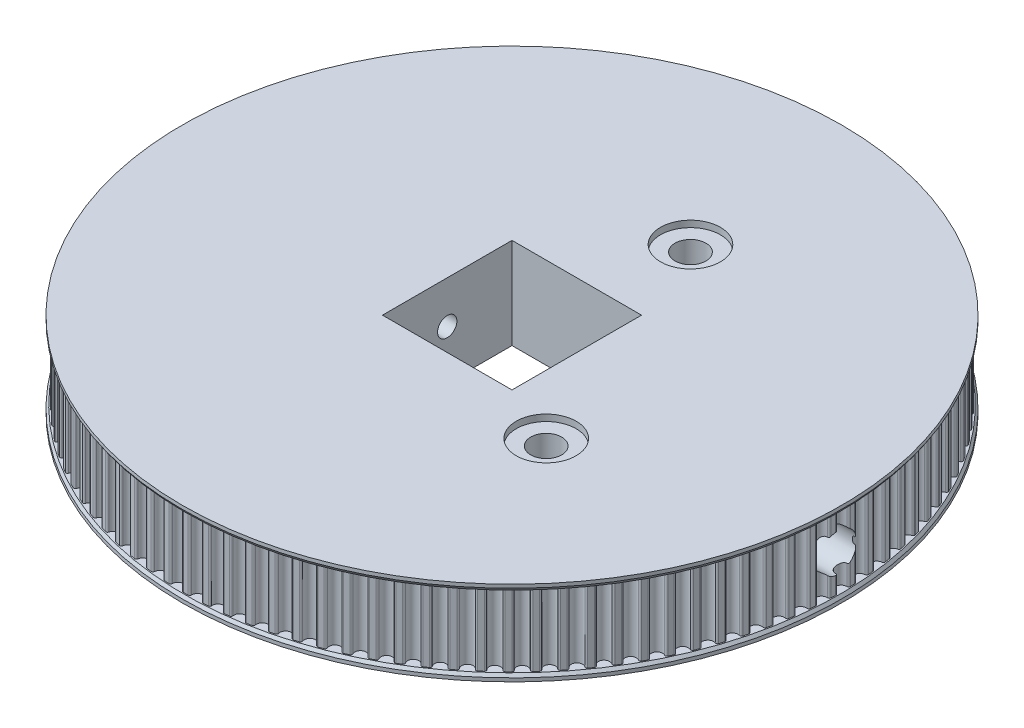
SolidWorks part; units mm, degrees
ref_plane "Front Plane" through (0, 0, 0) normal (0, 0, 1) x (1, 0, 0)
ref_plane "Top Plane" through (0, 0, 0) normal (0, 1, 0) x (1, 0, 0)
ref_plane "Right Plane" through (0, 0, 0) normal (1, 0, 0) x (0, 0, -1)
sketch "Sketch1" plane through (0, 0, 0) normal (0, 1, 0) x (1, 0, 0)
  arc A2 (0, 48.9563) -> (0.8696, 49.853) centre (0, 49.8263) ccw
  arc A3 (2.1134, 49.8158) -> (2.9278, 48.8687) centre (2.9798, 49.7371) ccw
  arc A4 (1.1354, 50.121) -> (0.8696, 49.853) centre (1.1295, 49.861) ccw
  arc A5 (2.1134, 49.8158) -> (1.8641, 50.0991) centre (1.8545, 49.8393) ccw
  arc A6 (1.8641, 50.0991) -> (1.1354, 50.121) centre (0, 0) ccw
  arc A7 (2.9278, 48.8687) -> (3.8495, 49.7118) centre (2.9798, 49.7371) ccw
  arc A8 (4.1308, 49.9633) -> (3.8495, 49.7118) centre (4.1093, 49.7042) ccw
  arc A9 (4.8569, 49.898) -> (4.1308, 49.9633) centre (0, 0) ccw
  arc A10 (5.0888, 49.6003) -> (4.8569, 49.898) centre (4.8317, 49.6392) ccw
  arc A11 (5.0888, 49.6003) -> (5.8451, 48.6061) centre (5.949, 49.4699) ccw
  arc A12 (5.8451, 48.6061) -> (6.8155, 49.3926) centre (5.949, 49.4699) ccw
  arc A13 (7.1114, 49.6269) -> (6.8155, 49.3926) centre (7.0745, 49.3695) ccw
  arc A14 (7.8323, 49.5182) -> (7.1114, 49.6269) centre (0, 0) ccw
  arc A15 (8.046, 49.2071) -> (7.8323, 49.5182) centre (7.7917, 49.2614) ccw
  arc A16 (8.046, 49.2071) -> (8.7415, 48.1696) centre (8.8968, 49.0256) ccw
  arc A17 (8.7415, 48.1696) -> (9.7572, 48.8966) centre (8.8968, 49.0256) ccw
  arc A18 (10.0666, 49.1128) -> (9.7572, 48.8966) centre (10.0143, 48.8581) ccw
  arc A19 (10.7797, 48.9612) -> (10.0666, 49.1128) centre (0, 0) ccw
  arc A20 (10.9744, 48.6379) -> (10.7797, 48.9612) centre (10.7238, 48.7073) ccw
  arc A21 (10.9744, 48.6379) -> (11.6066, 47.5606) centre (11.8128, 48.4058) ccw
  arc A22 (11.6066, 47.5606) -> (12.664, 48.2256) centre (11.8128, 48.4058) ccw
  arc A23 (12.9857, 48.4228) -> (12.664, 48.2256) centre (12.9183, 48.1717) ccw
  arc A24 (13.6885, 48.2289) -> (12.9857, 48.4228) centre (0, 0) ccw
  arc A25 (13.8635, 47.8945) -> (13.6885, 48.2289) centre (13.6175, 47.9787) ccw
  arc A26 (13.8635, 47.8945) -> (14.4301, 46.7813) centre (14.6866, 47.6127) ccw
  arc A27 (14.4301, 46.7813) -> (15.5254, 47.3819) centre (14.6866, 47.6127) ccw
  arc A28 (15.8583, 47.5596) -> (15.5254, 47.3819) centre (15.7761, 47.3129) ccw
  arc A29 (16.5483, 47.3239) -> (15.8583, 47.5596) centre (0, 0) ccw
  arc A30 (16.703, 46.9797) -> (16.5483, 47.3239) centre (16.4625, 47.0785) ccw
  arc A31 (16.703, 46.9797) -> (17.202, 45.8346) centre (17.5077, 46.6491) ccw
  arc A32 (17.202, 45.8346) -> (18.3312, 46.3686) centre (17.5077, 46.6491) ccw
  arc A33 (18.6742, 46.526) -> (18.3312, 46.3686) centre (18.5774, 46.2848) ccw
  arc A34 (19.3488, 46.2496) -> (18.6742, 46.526) centre (0, 0) ccw
  arc A35 (19.4826, 45.8967) -> (19.3488, 46.2496) centre (19.2485, 46.0097) ccw
  arc A36 (19.4826, 45.8967) -> (19.9123, 44.7238) centre (20.2662, 45.5186) ccw
  arc A37 (19.9123, 44.7238) -> (21.0715, 45.1893) centre (20.2662, 45.5186) ccw
  arc A38 (21.4232, 45.326) -> (21.0715, 45.1893) centre (21.3121, 45.0909) ccw
  arc A39 (22.0801, 45.0096) -> (21.4232, 45.326) centre (0, 0) ccw
  arc A40 (22.1926, 44.6494) -> (22.0801, 45.0096) centre (21.9656, 44.7762) ccw
  arc A41 (22.1926, 44.6494) -> (22.5514, 43.4529) centre (22.9521, 44.2251) ccw
  arc A42 (22.5514, 43.4529) -> (23.7363, 43.8483) centre (22.9521, 44.2251) ccw
  arc A43 (24.0956, 43.9637) -> (23.7363, 43.8483) centre (23.9706, 43.7356) ccw
  arc A44 (24.7324, 43.6086) -> (24.0956, 43.9637) centre (0, 0) ccw
  arc A45 (24.8231, 43.2423) -> (24.7324, 43.6086) centre (24.6041, 43.3824) ccw
  arc A46 (24.8231, 43.2423) -> (25.1097, 42.0265) centre (25.5559, 42.7733) ccw
  arc A47 (25.1097, 42.0265) -> (26.3161, 42.3503) centre (25.5559, 42.7733) ccw
  arc A48 (26.6816, 42.4439) -> (26.3161, 42.3503) centre (26.5433, 42.2238) ccw
  arc A49 (27.2961, 42.0514) -> (26.6816, 42.4439) centre (0, 0) ccw
  arc A50 (27.3647, 41.6804) -> (27.2961, 42.0514) centre (27.1545, 41.8334) ccw
  arc A51 (27.3647, 41.6804) -> (27.5781, 40.4496) centre (28.0682, 41.1684) ccw
  arc A52 (27.5781, 40.4496) -> (28.8017, 40.7006) centre (28.0682, 41.1684) ccw
  arc A53 (29.1722, 40.7723) -> (28.8017, 40.7006) centre (29.0209, 40.5609) ccw
  arc A54 (29.7621, 40.3438) -> (29.1722, 40.7723) centre (0, 0) ccw
  arc A55 (29.8084, 39.9692) -> (29.7621, 40.3438) centre (29.6077, 40.1345) ccw
  arc A56 (29.8084, 39.9692) -> (29.9478, 38.7279) centre (30.48, 39.4161) ccw
  arc A57 (29.9478, 38.7279) -> (31.1842, 38.9053) centre (30.48, 39.4161) ccw
  arc A58 (31.5583, 38.9547) -> (31.1842, 38.9053) centre (31.3947, 38.7527) ccw
  arc A59 (32.1215, 38.4917) -> (31.5583, 38.9547) centre (0, 0) ccw
  arc A60 (32.1454, 38.115) -> (32.1215, 38.4917) centre (31.9549, 38.292) ccw
  arc A61 (32.1454, 38.115) -> (32.2103, 36.8676) centre (32.7827, 37.5228) ccw
  arc A62 (32.2103, 36.8676) -> (33.4551, 36.9708) centre (32.7827, 37.5228) ccw
  arc A63 (33.8315, 36.9977) -> (33.4551, 36.9708) centre (33.6561, 36.8058) ccw
  arc A64 (34.366, 36.5018) -> (33.8315, 36.9977) centre (0, 0) ccw
  arc A65 (34.3673, 36.1244) -> (34.366, 36.5018) centre (34.1878, 36.3125) ccw
  arc A66 (34.3673, 36.1244) -> (34.3574, 34.8753) centre (34.968, 35.4951) ccw
  arc A67 (34.3574, 34.8753) -> (35.6062, 34.9038) centre (34.968, 35.4951) ccw
  arc A68 (35.9836, 34.9082) -> (35.6062, 34.9038) centre (35.797, 34.7271) ccw
  arc A69 (36.4874, 34.3812) -> (35.9836, 34.9082) centre (0, 0) ccw
  arc A70 (36.4662, 34.0044) -> (36.4874, 34.3812) centre (36.2982, 34.2029) ccw
  arc A71 (36.4662, 34.0044) -> (36.3816, 32.7582) centre (37.0282, 33.3403) ccw
  arc A72 (36.3816, 32.7582) -> (37.6299, 32.712) centre (37.0282, 33.3403) ccw
  arc A73 (38.0068, 32.6937) -> (37.6299, 32.712) centre (37.8097, 32.5242) ccw
  arc A74 (38.4783, 32.1376) -> (38.0068, 32.6937) centre (0, 0) ccw
  arc A75 (38.4345, 31.7627) -> (38.4783, 32.1376) centre (38.2787, 31.9709) ccw
  arc A76 (38.4345, 31.7627) -> (38.2756, 30.5238) centre (38.9558, 31.0662) ccw
  arc A77 (38.2756, 30.5238) -> (39.5188, 30.403) centre (38.9558, 31.0662) ccw
  arc A78 (39.894, 30.3622) -> (39.5188, 30.403) centre (39.6871, 30.2048) ccw
  arc A79 (40.3313, 29.7789) -> (39.894, 30.3622) centre (0, 0) ccw
  arc A80 (40.2652, 29.4073) -> (40.3313, 29.7789) centre (40.1222, 29.6244) ccw
  arc A81 (40.2652, 29.4073) -> (40.0325, 28.1801) centre (40.7439, 28.6809) ccw
  arc A82 (40.0325, 28.1801) -> (41.2663, 27.9852) centre (40.7439, 28.6809) ccw
  arc A83 (41.6384, 27.9221) -> (41.2663, 27.9852) centre (41.4225, 27.7773) ccw
  arc A84 (42.0401, 27.3136) -> (41.6384, 27.9221) centre (0, 0) ccw
  arc A85 (41.9519, 26.9467) -> (42.0401, 27.3136) centre (41.822, 27.1719) ccw
  arc A86 (41.9519, 26.9467) -> (41.6462, 25.7355) centre (42.3862, 26.1929) ccw
  arc A87 (41.6462, 25.7355) -> (42.8661, 25.4672) centre (42.3862, 26.1929) ccw
  arc A88 (43.2337, 25.3819) -> (42.8661, 25.4672) centre (43.0095, 25.2503) ccw
  arc A89 (43.5983, 24.7505) -> (43.2337, 25.3819) centre (0, 0) ccw
  arc A90 (43.4883, 24.3895) -> (43.5983, 24.7505) centre (43.3722, 24.6222) ccw
  arc A91 (43.4883, 24.3895) -> (43.1107, 23.1989) centre (43.8768, 23.6111) ccw
  arc A92 (43.1107, 23.1989) -> (44.3124, 22.858) centre (43.8768, 23.6111) ccw
  arc A93 (44.6743, 22.751) -> (44.3124, 22.858) centre (44.4426, 22.633) ccw
  arc A94 (45.0004, 22.0989) -> (44.6743, 22.751) centre (0, 0) ccw
  arc A95 (44.869, 21.7451) -> (45.0004, 22.0989) centre (44.767, 21.9843) ccw
  arc A96 (44.869, 21.7451) -> (44.4209, 20.5791) centre (45.2103, 20.9448) ccw
  arc A97 (44.4209, 20.5791) -> (45.6001, 20.1671) centre (45.2103, 20.9448) ccw
  arc A98 (45.9549, 20.0385) -> (45.6001, 20.1671) centre (45.7166, 19.9346) ccw
  arc A99 (46.2415, 19.3681) -> (45.9549, 20.0385) centre (0, 0) ccw
  arc A100 (46.0892, 19.0228) -> (46.2415, 19.3681) centre (46.0017, 19.2677) ccw
  arc A101 (46.0892, 19.0228) -> (45.5721, 17.8857) centre (46.382, 18.2036) ccw
  arc A102 (45.5721, 17.8857) -> (46.7246, 17.4039) centre (46.382, 18.2036) ccw
  arc A103 (47.0711, 17.2544) -> (46.7246, 17.4039) centre (46.827, 17.1649) ccw
  arc A104 (47.317, 16.568) -> (47.0711, 17.2544) centre (0, 0) ccw
  arc A105 (47.1443, 16.2325) -> (47.317, 16.568) centre (47.0716, 16.4821) ccw
  arc A106 (47.1443, 16.2325) -> (46.5602, 15.1283) centre (47.3876, 15.3972) ccw
  arc A107 (46.5602, 15.1283) -> (47.6818, 14.5784) centre (47.3876, 15.3972) ccw
  arc A108 (48.0187, 14.4084) -> (47.6818, 14.5784) centre (47.7697, 14.3337) ccw
  arc A109 (48.2232, 13.7086) -> (48.0187, 14.4084) centre (0, 0) ccw
  arc A110 (48.0307, 13.384) -> (48.2232, 13.7086) centre (47.9731, 13.6375) ccw
  arc A111 (48.0307, 13.384) -> (47.3816, 12.3168) centre (48.2236, 12.5356) ccw
  arc A112 (47.3816, 12.3168) -> (48.4683, 11.7007) centre (48.2236, 12.5356) ccw
  arc A113 (48.7944, 11.5109) -> (48.4683, 11.7007) centre (48.5414, 11.4512) ccw
  arc A114 (48.9567, 10.8001) -> (48.7944, 11.5109) centre (0, 0) ccw
  arc A115 (48.7452, 10.4876) -> (48.9567, 10.8001) centre (48.7028, 10.7441) ccw
  arc A116 (48.7452, 10.4876) -> (48.0334, 9.4611) centre (48.887, 9.6292) ccw
  arc A117 (48.0334, 9.4611) -> (49.0813, 8.7812) centre (48.887, 9.6292) ccw
  arc A118 (49.3955, 8.5722) -> (49.0813, 8.7812) centre (49.1393, 8.5278) ccw
  arc A119 (49.5149, 7.853) -> (49.3955, 8.5722) centre (0, 0) ccw
  arc A120 (49.2851, 7.5537) -> (49.5149, 7.853) centre (49.2582, 7.8123) ccw
  arc A121 (49.2851, 7.5537) -> (48.5132, 6.5716) centre (49.3754, 6.6883) ccw
  arc A122 (48.5132, 6.5716) -> (49.5186, 5.8302) centre (49.3754, 6.6883) ccw
  arc A123 (49.8197, 5.6028) -> (49.5186, 5.8302) centre (49.5614, 5.5738) ccw
  arc A124 (49.896, 4.8777) -> (49.8197, 5.6028) centre (0, 0) ccw
  arc A125 (49.6486, 4.5927) -> (49.896, 4.8777) centre (49.6372, 4.8524) ccw
  arc A126 (49.6486, 4.5927) -> (48.8194, 3.6585) centre (49.687, 3.7235) ccw
  arc A127 (48.8194, 3.6585) -> (49.7786, 2.8584) centre (49.687, 3.7235) ccw
  arc A128 (50.0656, 2.6134) -> (49.7786, 2.8584) centre (49.806, 2.5998) ccw
  arc A129 (50.0984, 1.885) -> (50.0656, 2.6134) centre (0, 0) ccw
  arc A130 (49.8344, 1.6153) -> (50.0984, 1.885) centre (49.8385, 1.8752) ccw
  arc A131 (49.8344, 1.6153) -> (48.9508, 0.7324) centre (49.8207, 0.7454) ccw
  arc A132 (48.9508, 0.7324) -> (49.8605, -0.1237) centre (49.8207, 0.7454) ccw
  arc A133 (50.1323, -0.3854) -> (49.8605, -0.1237) centre (49.8723, -0.3834) ccw
  arc A134 (50.1214, -1.1145) -> (50.1323, -0.3854) centre (0, 0) ccw
  arc A135 (49.8418, -1.3679) -> (50.1214, -1.1145) centre (49.8615, -1.1087) ccw
  arc A136 (49.8418, -1.3679) -> (48.907, -2.1964) centre (49.7761, -2.2354) ccw
  arc A137 (48.907, -2.1964) -> (49.7638, -3.1054) centre (49.7761, -2.2354) ccw
  arc A138 (50.0195, -3.3829) -> (49.7638, -3.1054) centre (49.7601, -3.3653) ccw
  arc A139 (49.9651, -4.1099) -> (50.0195, -3.3829) centre (0, 0) ccw
  arc A140 (49.6708, -4.3462) -> (49.9651, -4.1099) centre (49.7059, -4.0886) ccw
  arc A141 (49.6708, -4.3462) -> (48.6881, -5.1173) centre (49.5534, -5.2083) ccw
  arc A142 (48.6881, -5.1173) -> (49.489, -6.0759) centre (49.5534, -5.2083) ccw
  arc A143 (49.7277, -6.3682) -> (49.489, -6.0759) centre (49.4698, -6.3352) ccw
  arc A144 (49.6298, -7.0907) -> (49.7277, -6.3682) centre (0, 0) ccw
  arc A145 (49.322, -7.309) -> (49.6298, -7.0907) centre (49.3725, -7.0539) ccw
  arc A146 (49.322, -7.309) -> (48.2949, -8.0199) centre (49.1532, -8.1624) ccw
  arc A147 (48.2949, -8.0199) -> (49.0371, -9.0247) centre (49.1532, -8.1624) ccw
  arc A148 (49.2579, -9.3307) -> (49.0371, -9.0247) centre (49.0024, -9.2823) ccw
  arc A149 (49.117, -10.0461) -> (49.2579, -9.3307) centre (0, 0) ccw
  arc A150 (48.7966, -10.2456) -> (49.117, -10.0461) centre (48.8622, -9.994) ccw
  arc A151 (48.7966, -10.2456) -> (47.7289, -10.8938) centre (48.5771, -11.0874) ccw
  arc A152 (47.7289, -10.8938) -> (48.4096, -11.9411) centre (48.5771, -11.0874) ccw
  arc A153 (48.6117, -12.2598) -> (48.4096, -11.9411) centre (48.3596, -12.1963) ccw
  arc A154 (48.4282, -12.9655) -> (48.6117, -12.2598) centre (0, 0) ccw
  arc A155 (48.0965, -13.1455) -> (48.4282, -12.9655) centre (48.1771, -12.8982) ccw
  arc A156 (48.0965, -13.1455) -> (46.9919, -13.7287) centre (47.827, -13.9727) ccw
  arc A157 (46.9919, -13.7287) -> (47.6088, -14.8149) centre (47.827, -13.9727) ccw
  arc A158 (47.7915, -15.1451) -> (47.6088, -14.8149) centre (47.5436, -15.0665) ccw
  arc A159 (47.5662, -15.8385) -> (47.7915, -15.1451) centre (0, 0) ccw
  arc A160 (47.2243, -15.9983) -> (47.5662, -15.8385) centre (47.3195, -15.7564) ccw
  arc A161 (47.2243, -15.9983) -> (46.0868, -16.5144) centre (46.9058, -16.8079) ccw
  arc A162 (46.0868, -16.5144) -> (46.6376, -17.6355) centre (46.9058, -16.8079) ccw
  arc A163 (46.8002, -17.9761) -> (46.6376, -17.6355) centre (46.5575, -17.8829) ccw
  arc A164 (46.5338, -18.6548) -> (46.8002, -17.9761) centre (0, 0) ccw
  arc A165 (46.183, -18.7939) -> (46.5338, -18.6548) centre (46.2925, -18.5581) ccw
  arc A166 (46.183, -18.7939) -> (45.0167, -19.2411) centre (45.8167, -19.583) ccw
  arc A167 (45.0167, -19.2411) -> (45.4995, -20.3931) centre (45.8167, -19.583) ccw
  arc A168 (45.6414, -20.7428) -> (45.4995, -20.3931) centre (45.4047, -20.6352) ccw
  arc A169 (45.3349, -21.4043) -> (45.6414, -20.7428) centre (0, 0) ccw
  arc A170 (44.9764, -21.5222) -> (45.3349, -21.4043) centre (45.0998, -21.2933) ccw
  arc A171 (44.9764, -21.5222) -> (43.7854, -21.8988) centre (44.5635, -22.288) ccw
  arc A172 (43.7854, -21.8988) -> (44.1984, -23.0777) centre (44.5635, -22.288) ccw
  arc A173 (44.3192, -23.4352) -> (44.1984, -23.0777) centre (44.0893, -23.3137) ccw
  arc A174 (43.9737, -24.0772) -> (44.3192, -23.4352) centre (0, 0) ccw
  arc A175 (43.6088, -24.1734) -> (43.9737, -24.0772) centre (43.7456, -23.9524) ccw
  arc A176 (43.6088, -24.1734) -> (42.3974, -24.4782) centre (43.1508, -24.9132) ccw
  arc A177 (42.3974, -24.4782) -> (42.7392, -25.6796) centre (43.1508, -24.9132) ccw
  arc A178 (42.8383, -26.0437) -> (42.7392, -25.6796) centre (42.6162, -25.9087) ccw
  arc A179 (42.4551, -26.6639) -> (42.8383, -26.0437) centre (0, 0) ccw
  arc A180 (42.0851, -26.7381) -> (42.4551, -26.6639) centre (42.2349, -26.5257) ccw
  arc A181 (42.0851, -26.7381) -> (40.8576, -26.9699) centre (41.5837, -27.4492) ccw
  arc A182 (40.8576, -26.9699) -> (41.127, -28.1896) centre (41.5837, -27.4492) ccw
  arc A183 (41.2041, -28.559) -> (41.127, -28.1896) centre (40.9905, -28.4109) ccw
  arc A184 (40.7845, -29.1552) -> (41.2041, -28.559) centre (0, 0) ccw
  arc A185 (40.4107, -29.2072) -> (40.7845, -29.1552) centre (40.573, -29.004) ccw
  arc A186 (40.4107, -29.2072) -> (39.1716, -29.3651) centre (39.8677, -29.8869) ccw
  arc A187 (39.1716, -29.3651) -> (39.3675, -30.5987) centre (39.8677, -29.8869) ccw
  arc A188 (39.4224, -30.9721) -> (39.3675, -30.5987) centre (39.218, -30.8115) ccw
  arc A189 (38.9679, -31.5421) -> (39.4224, -30.9721) centre (0, 0) ccw
  arc A190 (38.5916, -31.5716) -> (38.9679, -31.5421) centre (38.7658, -31.3785) ccw
  arc A191 (38.5916, -31.5716) -> (37.3453, -31.6551) centre (38.009, -32.2177) ccw
  arc A192 (37.3453, -31.6551) -> (37.4671, -32.8983) centre (38.009, -32.2177) ccw
  arc A193 (37.4996, -33.2743) -> (37.4671, -32.8983) centre (37.3051, -33.1017) ccw
  arc A194 (37.0118, -33.8161) -> (37.4996, -33.2743) centre (0, 0) ccw
  arc A195 (36.6345, -33.823) -> (37.0118, -33.8161) centre (36.8198, -33.6407) ccw
  arc A196 (36.6345, -33.823) -> (35.3854, -33.8319) centre (36.0142, -34.4331) ccw
  arc A197 (35.3854, -33.8319) -> (35.4326, -35.0801) centre (36.0142, -34.4331) ccw
  arc A198 (35.4426, -35.4573) -> (35.4326, -35.0801) centre (35.2588, -35.2735) ccw
  arc A199 (34.9232, -35.969) -> (35.4426, -35.4573) centre (0, 0) ccw
  arc A200 (34.5461, -35.9534) -> (34.9232, -35.969) centre (34.7421, -35.7825) ccw
  arc A201 (34.5461, -35.9534) -> (33.2987, -35.8875) centre (33.8905, -36.5253) ccw
  arc A202 (33.2987, -35.8875) -> (33.2712, -37.1363) centre (33.8905, -36.5253) ccw
  arc A203 (33.2586, -37.5135) -> (33.2712, -37.1363) centre (33.0861, -37.3189) ccw
  arc A204 (32.7096, -37.9932) -> (33.2586, -37.5135) centre (0, 0) ccw
  arc A205 (32.3341, -37.955) -> (32.7096, -37.9932) centre (32.5399, -37.7962) ccw
  arc A206 (32.3341, -37.955) -> (31.0929, -37.8147) centre (31.6455, -38.4867) ccw
  arc A207 (31.0929, -37.8147) -> (30.9908, -39.0596) centre (31.6455, -38.4867) ccw
  arc A208 (30.9556, -39.4354) -> (30.9908, -39.0596) centre (30.7951, -39.2308) ccw
  arc A209 (30.3789, -39.8814) -> (30.9556, -39.4354) centre (0, 0) ccw
  arc A210 (30.0064, -39.8208) -> (30.3789, -39.8814) centre (30.2213, -39.6745) ccw
  arc A211 (30.0064, -39.8208) -> (28.7758, -39.6065) centre (29.2872, -40.3103) ccw
  arc A212 (28.7758, -39.6065) -> (28.5994, -40.8431) centre (29.2872, -40.3103) ccw
  arc A213 (28.5418, -41.216) -> (28.5994, -40.8431) centre (28.3938, -41.0023) ccw
  arc A214 (27.9394, -41.6268) -> (28.5418, -41.216) centre (0, 0) ccw
  arc A215 (27.5712, -41.544) -> (27.9394, -41.6268) centre (27.7945, -41.4109) ccw
  arc A216 (27.5712, -41.544) -> (26.3557, -41.2565) centre (26.824, -41.9897) ccw
  arc A217 (26.3557, -41.2565) -> (26.1056, -42.4803) centre (26.824, -41.9897) ccw
  arc A218 (26.0259, -42.8492) -> (26.1056, -42.4803) centre (25.8909, -42.627) ccw
  arc A219 (25.4, -43.2231) -> (26.0259, -42.8492) centre (0, 0) ccw
  arc A220 (25.0374, -43.1186) -> (25.4, -43.2231) centre (25.2682, -42.999) ccw
  arc A221 (25.0374, -43.1186) -> (23.8412, -42.7588) centre (24.2649, -43.5187) ccw
  arc A222 (23.8412, -42.7588) -> (23.5184, -43.9655) centre (24.2649, -43.5187) ccw
  arc A223 (23.4167, -44.329) -> (23.5184, -43.9655) centre (23.2953, -44.0991) ccw
  arc A224 (22.7696, -44.6648) -> (23.4167, -44.329) centre (0, 0) ccw
  arc A225 (22.4139, -44.5387) -> (22.7696, -44.6648) centre (22.6515, -44.4332) ccw
  arc A226 (22.4139, -44.5387) -> (21.2413, -44.1081) centre (21.6188, -44.892) ccw
  arc A227 (21.2413, -44.1081) -> (20.8469, -45.2933) centre (21.6188, -44.892) ccw
  arc A228 (20.7237, -45.65) -> (20.8469, -45.2933) centre (20.6163, -45.4133) ccw
  arc A229 (20.0577, -45.9466) -> (20.7237, -45.65) centre (0, 0) ccw
  arc A230 (19.7102, -45.7995) -> (20.0577, -45.9466) centre (19.9537, -45.7083) ccw
  arc A231 (19.7102, -45.7995) -> (18.5655, -45.2995) centre (18.8954, -46.1045) ccw
  arc A232 (18.5655, -45.2995) -> (18.1009, -46.459) centre (18.8954, -46.1045) ccw
  arc A233 (17.9566, -46.8077) -> (18.1009, -46.459) centre (17.8635, -46.5649) ccw
  arc A234 (17.274, -47.0639) -> (17.9566, -46.8077) centre (0, 0) ccw
  arc A235 (16.9359, -46.8962) -> (17.274, -47.0639) centre (17.1844, -46.8198) ccw
  arc A236 (16.9359, -46.8962) -> (15.8232, -46.3287) centre (16.1043, -47.152) ccw
  arc A237 (15.8232, -46.3287) -> (15.2901, -47.4583) centre (16.1043, -47.152) ccw
  arc A238 (15.1252, -47.7978) -> (15.2901, -47.4583) centre (15.0467, -47.5499) ccw
  arc A239 (14.4285, -48.0127) -> (15.1252, -47.7978) centre (0, 0) ccw
  arc A240 (14.101, -47.8251) -> (14.4285, -48.0127) centre (14.3536, -47.7637) ccw
  arc A241 (14.101, -47.8251) -> (13.0242, -47.1921) centre (13.2556, -48.0307) ccw
  arc A242 (13.0242, -47.1921) -> (12.4245, -48.2878) centre (13.2556, -48.0307) ccw
  arc A243 (12.2396, -48.6168) -> (12.4245, -48.2878) centre (12.1761, -48.3646) ccw
  arc A244 (11.5313, -48.7896) -> (12.2396, -48.6168) centre (0, 0) ccw
  arc A245 (11.2156, -48.5828) -> (11.5313, -48.7896) centre (11.4715, -48.5366) ccw
  arc A246 (11.2156, -48.5828) -> (10.1786, -47.8865) centre (10.3595, -48.7375) ccw
  arc A247 (10.1786, -47.8865) -> (9.5144, -48.9444) centre (10.3595, -48.7375) ccw
  arc A248 (9.3102, -49.2617) -> (9.5144, -48.9444) centre (9.2619, -49.0063) ccw
  arc A249 (8.5928, -49.3919) -> (9.3102, -49.2617) centre (0, 0) ccw
  arc A250 (8.2901, -49.1666) -> (8.5928, -49.3919) centre (8.5483, -49.1358) ccw
  arc A251 (8.2901, -49.1666) -> (7.2966, -48.4095) centre (7.4262, -49.2698) ccw
  arc A252 (7.2966, -48.4095) -> (6.5703, -49.4258) centre (7.4262, -49.2698) ccw
  arc A253 (6.3475, -49.7304) -> (6.5703, -49.4258) centre (6.3145, -49.4724) ccw
  arc A254 (5.6236, -49.8174) -> (6.3475, -49.7304) centre (0, 0) ccw
  arc A255 (5.3349, -49.5744) -> (5.6236, -49.8174) centre (5.5944, -49.559) ccw
  arc A256 (5.3349, -49.5744) -> (4.3884, -48.7592) centre (4.4664, -49.6257) ccw
  arc A257 (4.3884, -48.7592) -> (3.6027, -49.7303) centre (4.4664, -49.6257) ccw
  arc A258 (3.362, -50.021) -> (3.6027, -49.7303) centre (3.3446, -49.7615) ccw
  arc A259 (2.6342, -50.0646) -> (3.362, -50.021) centre (0, 0) ccw
  arc A260 (2.3606, -49.8047) -> (2.6342, -50.0646) centre (2.6206, -49.8049) ccw
  arc A261 (2.3606, -49.8047) -> (1.4646, -48.9344) centre (1.4906, -49.804) ccw
  arc A262 (1.4646, -48.9344) -> (0.6222, -49.8567) centre (1.4906, -49.804) ccw
  arc A263 (0.3645, -50.1325) -> (0.6222, -49.8567) centre (0.3627, -49.8725) ccw
  arc A264 (-0.3645, -50.1325) -> (0.3645, -50.1325) centre (0, 0) ccw
  arc A265 (-0.6222, -49.8567) -> (-0.3645, -50.1325) centre (-0.3627, -49.8725) ccw
  arc A266 (-0.6222, -49.8567) -> (-1.4646, -48.9344) centre (-1.4906, -49.804) ccw
  arc A267 (-1.4646, -48.9344) -> (-2.3606, -49.8047) centre (-1.4906, -49.804) ccw
  arc A268 (-2.6342, -50.0646) -> (-2.3606, -49.8047) centre (-2.6206, -49.8049) ccw
  arc A269 (-3.362, -50.021) -> (-2.6342, -50.0646) centre (0, 0) ccw
  arc A270 (-3.6027, -49.7303) -> (-3.362, -50.021) centre (-3.3446, -49.7615) ccw
  arc A271 (-3.6027, -49.7303) -> (-4.3884, -48.7592) centre (-4.4664, -49.6257) ccw
  arc A272 (-4.3884, -48.7592) -> (-5.3349, -49.5744) centre (-4.4664, -49.6257) ccw
  arc A273 (-5.6236, -49.8174) -> (-5.3349, -49.5744) centre (-5.5944, -49.559) ccw
  arc A274 (-6.3475, -49.7304) -> (-5.6236, -49.8174) centre (0, 0) ccw
  arc A275 (-6.5703, -49.4258) -> (-6.3475, -49.7304) centre (-6.3145, -49.4724) ccw
  arc A276 (-6.5703, -49.4258) -> (-7.2966, -48.4095) centre (-7.4262, -49.2698) ccw
  arc A277 (-7.2966, -48.4095) -> (-8.2901, -49.1666) centre (-7.4262, -49.2698) ccw
  arc A278 (-8.5928, -49.3919) -> (-8.2901, -49.1666) centre (-8.5483, -49.1358) ccw
  arc A279 (-9.3102, -49.2617) -> (-8.5928, -49.3919) centre (0, 0) ccw
  arc A280 (-9.5144, -48.9444) -> (-9.3102, -49.2617) centre (-9.2619, -49.0063) ccw
  arc A281 (-9.5144, -48.9444) -> (-10.1786, -47.8865) centre (-10.3595, -48.7375) ccw
  arc A282 (-10.1786, -47.8865) -> (-11.2156, -48.5828) centre (-10.3595, -48.7375) ccw
  arc A283 (-11.5313, -48.7896) -> (-11.2156, -48.5828) centre (-11.4715, -48.5366) ccw
  arc A284 (-12.2396, -48.6168) -> (-11.5313, -48.7896) centre (0, 0) ccw
  arc A285 (-12.4245, -48.2878) -> (-12.2396, -48.6168) centre (-12.1761, -48.3646) ccw
  arc A286 (-12.4245, -48.2878) -> (-13.0242, -47.1921) centre (-13.2556, -48.0307) ccw
  arc A287 (-13.0242, -47.1921) -> (-14.101, -47.8251) centre (-13.2556, -48.0307) ccw
  arc A288 (-14.4285, -48.0127) -> (-14.101, -47.8251) centre (-14.3536, -47.7637) ccw
  arc A289 (-15.1252, -47.7978) -> (-14.4285, -48.0127) centre (0, 0) ccw
  arc A290 (-15.2901, -47.4583) -> (-15.1252, -47.7978) centre (-15.0467, -47.5499) ccw
  arc A291 (-15.2901, -47.4583) -> (-15.8232, -46.3287) centre (-16.1043, -47.152) ccw
  arc A292 (-15.8232, -46.3287) -> (-16.9359, -46.8962) centre (-16.1043, -47.152) ccw
  arc A293 (-17.274, -47.0639) -> (-16.9359, -46.8962) centre (-17.1844, -46.8198) ccw
  arc A294 (-17.9566, -46.8077) -> (-17.274, -47.0639) centre (0, 0) ccw
  arc A295 (-18.1009, -46.459) -> (-17.9566, -46.8077) centre (-17.8635, -46.5649) ccw
  arc A296 (-18.1009, -46.459) -> (-18.5655, -45.2995) centre (-18.8954, -46.1045) ccw
  arc A297 (-18.5655, -45.2995) -> (-19.7102, -45.7995) centre (-18.8954, -46.1045) ccw
  arc A298 (-20.0577, -45.9466) -> (-19.7102, -45.7995) centre (-19.9537, -45.7083) ccw
  arc A299 (-20.7237, -45.65) -> (-20.0577, -45.9466) centre (0, 0) ccw
  arc A300 (-20.8469, -45.2933) -> (-20.7237, -45.65) centre (-20.6163, -45.4133) ccw
  arc A301 (-20.8469, -45.2933) -> (-21.2413, -44.1081) centre (-21.6188, -44.892) ccw
  arc A302 (-21.2413, -44.1081) -> (-22.4139, -44.5387) centre (-21.6188, -44.892) ccw
  arc A303 (-22.7696, -44.6648) -> (-22.4139, -44.5387) centre (-22.6515, -44.4332) ccw
  arc A304 (-23.4167, -44.329) -> (-22.7696, -44.6648) centre (0, 0) ccw
  arc A305 (-23.5184, -43.9655) -> (-23.4167, -44.329) centre (-23.2953, -44.0991) ccw
  arc A306 (-23.5184, -43.9655) -> (-23.8412, -42.7588) centre (-24.2649, -43.5187) ccw
  arc A307 (-23.8412, -42.7588) -> (-25.0374, -43.1186) centre (-24.2649, -43.5187) ccw
  arc A308 (-25.4, -43.2231) -> (-25.0374, -43.1186) centre (-25.2682, -42.999) ccw
  arc A309 (-26.0259, -42.8492) -> (-25.4, -43.2231) centre (0, 0) ccw
  arc A310 (-26.1056, -42.4803) -> (-26.0259, -42.8492) centre (-25.8909, -42.627) ccw
  arc A311 (-26.1056, -42.4803) -> (-26.3557, -41.2565) centre (-26.824, -41.9897) ccw
  arc A312 (-26.3557, -41.2565) -> (-27.5712, -41.544) centre (-26.824, -41.9897) ccw
  arc A313 (-27.9394, -41.6268) -> (-27.5712, -41.544) centre (-27.7945, -41.4109) ccw
  arc A314 (-28.5418, -41.216) -> (-27.9394, -41.6268) centre (0, 0) ccw
  arc A315 (-28.5994, -40.8431) -> (-28.5418, -41.216) centre (-28.3938, -41.0023) ccw
  arc A316 (-28.5994, -40.8431) -> (-28.7758, -39.6065) centre (-29.2872, -40.3103) ccw
  arc A317 (-28.7758, -39.6065) -> (-30.0064, -39.8208) centre (-29.2872, -40.3103) ccw
  arc A318 (-30.3789, -39.8814) -> (-30.0064, -39.8208) centre (-30.2213, -39.6745) ccw
  arc A319 (-30.9556, -39.4354) -> (-30.3789, -39.8814) centre (0, 0) ccw
  arc A320 (-30.9908, -39.0596) -> (-30.9556, -39.4354) centre (-30.7951, -39.2308) ccw
  arc A321 (-30.9908, -39.0596) -> (-31.0929, -37.8147) centre (-31.6455, -38.4867) ccw
  arc A322 (-31.0929, -37.8147) -> (-32.3341, -37.955) centre (-31.6455, -38.4867) ccw
  arc A323 (-32.7096, -37.9932) -> (-32.3341, -37.955) centre (-32.5399, -37.7962) ccw
  arc A324 (-33.2586, -37.5135) -> (-32.7096, -37.9932) centre (0, 0) ccw
  arc A325 (-33.2712, -37.1363) -> (-33.2586, -37.5135) centre (-33.0861, -37.3189) ccw
  arc A326 (-33.2712, -37.1363) -> (-33.2987, -35.8875) centre (-33.8905, -36.5253) ccw
  arc A327 (-33.2987, -35.8875) -> (-34.5461, -35.9534) centre (-33.8905, -36.5253) ccw
  arc A328 (-34.9232, -35.969) -> (-34.5461, -35.9534) centre (-34.7421, -35.7825) ccw
  arc A329 (-35.4426, -35.4573) -> (-34.9232, -35.969) centre (0, 0) ccw
  arc A330 (-35.4326, -35.0801) -> (-35.4426, -35.4573) centre (-35.2588, -35.2735) ccw
  arc A331 (-35.4326, -35.0801) -> (-35.3854, -33.8319) centre (-36.0142, -34.4331) ccw
  arc A332 (-35.3854, -33.8319) -> (-36.6345, -33.823) centre (-36.0142, -34.4331) ccw
  arc A333 (-37.0118, -33.8161) -> (-36.6345, -33.823) centre (-36.8198, -33.6407) ccw
  arc A334 (-37.4996, -33.2743) -> (-37.0118, -33.8161) centre (0, 0) ccw
  arc A335 (-37.4671, -32.8983) -> (-37.4996, -33.2743) centre (-37.3051, -33.1017) ccw
  arc A336 (-37.4671, -32.8983) -> (-37.3453, -31.6551) centre (-38.009, -32.2177) ccw
  arc A337 (-37.3453, -31.6551) -> (-38.5916, -31.5716) centre (-38.009, -32.2177) ccw
  arc A338 (-38.9679, -31.5421) -> (-38.5916, -31.5716) centre (-38.7658, -31.3785) ccw
  arc A339 (-39.4224, -30.9721) -> (-38.9679, -31.5421) centre (0, 0) ccw
  arc A340 (-39.3675, -30.5987) -> (-39.4224, -30.9721) centre (-39.218, -30.8115) ccw
  arc A341 (-39.3675, -30.5987) -> (-39.1716, -29.3651) centre (-39.8677, -29.8869) ccw
  arc A342 (-39.1716, -29.3651) -> (-40.4107, -29.2072) centre (-39.8677, -29.8869) ccw
  arc A343 (-40.7845, -29.1552) -> (-40.4107, -29.2072) centre (-40.573, -29.004) ccw
  arc A344 (-41.2041, -28.559) -> (-40.7845, -29.1552) centre (0, 0) ccw
  arc A345 (-41.127, -28.1896) -> (-41.2041, -28.559) centre (-40.9905, -28.4109) ccw
  arc A346 (-41.127, -28.1896) -> (-40.8576, -26.9699) centre (-41.5837, -27.4492) ccw
  arc A347 (-40.8576, -26.9699) -> (-42.0851, -26.7381) centre (-41.5837, -27.4492) ccw
  arc A348 (-42.4551, -26.6639) -> (-42.0851, -26.7381) centre (-42.2349, -26.5257) ccw
  arc A349 (-42.8383, -26.0437) -> (-42.4551, -26.6639) centre (0, 0) ccw
  arc A350 (-42.7392, -25.6796) -> (-42.8383, -26.0437) centre (-42.6162, -25.9087) ccw
  arc A351 (-42.7392, -25.6796) -> (-42.3974, -24.4782) centre (-43.1508, -24.9132) ccw
  arc A352 (-42.3974, -24.4782) -> (-43.6088, -24.1734) centre (-43.1508, -24.9132) ccw
  arc A353 (-43.9737, -24.0772) -> (-43.6088, -24.1734) centre (-43.7456, -23.9524) ccw
  arc A354 (-44.3192, -23.4352) -> (-43.9737, -24.0772) centre (0, 0) ccw
  arc A355 (-44.1984, -23.0777) -> (-44.3192, -23.4352) centre (-44.0893, -23.3137) ccw
  arc A356 (-44.1984, -23.0777) -> (-43.7854, -21.8988) centre (-44.5635, -22.288) ccw
  arc A357 (-43.7854, -21.8988) -> (-44.9764, -21.5222) centre (-44.5635, -22.288) ccw
  arc A358 (-45.3349, -21.4043) -> (-44.9764, -21.5222) centre (-45.0998, -21.2933) ccw
  arc A359 (-45.6414, -20.7428) -> (-45.3349, -21.4043) centre (0, 0) ccw
  arc A360 (-45.4995, -20.3931) -> (-45.6414, -20.7428) centre (-45.4047, -20.6352) ccw
  arc A361 (-45.4995, -20.3931) -> (-45.0167, -19.2411) centre (-45.8167, -19.583) ccw
  arc A362 (-45.0167, -19.2411) -> (-46.183, -18.7939) centre (-45.8167, -19.583) ccw
  arc A363 (-46.5338, -18.6548) -> (-46.183, -18.7939) centre (-46.2925, -18.5581) ccw
  arc A364 (-46.8002, -17.9761) -> (-46.5338, -18.6548) centre (0, 0) ccw
  arc A365 (-46.6376, -17.6355) -> (-46.8002, -17.9761) centre (-46.5575, -17.8829) ccw
  arc A366 (-46.6376, -17.6355) -> (-46.0868, -16.5144) centre (-46.9058, -16.8079) ccw
  arc A367 (-46.0868, -16.5144) -> (-47.2243, -15.9983) centre (-46.9058, -16.8079) ccw
  arc A368 (-47.5662, -15.8385) -> (-47.2243, -15.9983) centre (-47.3195, -15.7564) ccw
  arc A369 (-47.7915, -15.1451) -> (-47.5662, -15.8385) centre (0, 0) ccw
  arc A370 (-47.6088, -14.8149) -> (-47.7915, -15.1451) centre (-47.5436, -15.0665) ccw
  arc A371 (-47.6088, -14.8149) -> (-46.9919, -13.7287) centre (-47.827, -13.9727) ccw
  arc A372 (-46.9919, -13.7287) -> (-48.0965, -13.1455) centre (-47.827, -13.9727) ccw
  arc A373 (-48.4282, -12.9655) -> (-48.0965, -13.1455) centre (-48.1771, -12.8982) ccw
  arc A374 (-48.6117, -12.2598) -> (-48.4282, -12.9655) centre (0, 0) ccw
  arc A375 (-48.4096, -11.9411) -> (-48.6117, -12.2598) centre (-48.3596, -12.1963) ccw
  arc A376 (-48.4096, -11.9411) -> (-47.7289, -10.8938) centre (-48.5771, -11.0874) ccw
  arc A377 (-47.7289, -10.8938) -> (-48.7966, -10.2456) centre (-48.5771, -11.0874) ccw
  arc A378 (-49.117, -10.0461) -> (-48.7966, -10.2456) centre (-48.8622, -9.994) ccw
  arc A379 (-49.2579, -9.3307) -> (-49.117, -10.0461) centre (0, 0) ccw
  arc A380 (-49.0371, -9.0247) -> (-49.2579, -9.3307) centre (-49.0024, -9.2823) ccw
  arc A381 (-49.0371, -9.0247) -> (-48.2949, -8.0199) centre (-49.1532, -8.1624) ccw
  arc A382 (-48.2949, -8.0199) -> (-49.322, -7.309) centre (-49.1532, -8.1624) ccw
  arc A383 (-49.6298, -7.0907) -> (-49.322, -7.309) centre (-49.3725, -7.0539) ccw
  arc A384 (-49.7277, -6.3682) -> (-49.6298, -7.0907) centre (0, 0) ccw
  arc A385 (-49.489, -6.0759) -> (-49.7277, -6.3682) centre (-49.4698, -6.3352) ccw
  arc A386 (-49.489, -6.0759) -> (-48.6881, -5.1173) centre (-49.5534, -5.2083) ccw
  arc A387 (-48.6881, -5.1173) -> (-49.6708, -4.3462) centre (-49.5534, -5.2083) ccw
  arc A388 (-49.9651, -4.1099) -> (-49.6708, -4.3462) centre (-49.7059, -4.0886) ccw
  arc A389 (-50.0195, -3.3829) -> (-49.9651, -4.1099) centre (0, 0) ccw
  arc A390 (-49.7638, -3.1054) -> (-50.0195, -3.3829) centre (-49.7601, -3.3653) ccw
  arc A391 (-49.7638, -3.1054) -> (-48.907, -2.1964) centre (-49.7761, -2.2354) ccw
  arc A392 (-48.907, -2.1964) -> (-49.8418, -1.3679) centre (-49.7761, -2.2354) ccw
  arc A393 (-50.1214, -1.1145) -> (-49.8418, -1.3679) centre (-49.8615, -1.1087) ccw
  arc A394 (-50.1323, -0.3854) -> (-50.1214, -1.1145) centre (0, 0) ccw
  arc A395 (-49.8605, -0.1237) -> (-50.1323, -0.3854) centre (-49.8723, -0.3834) ccw
  arc A396 (-49.8605, -0.1237) -> (-48.9508, 0.7324) centre (-49.8207, 0.7454) ccw
  arc A397 (-48.9508, 0.7324) -> (-49.8344, 1.6153) centre (-49.8207, 0.7454) ccw
  arc A398 (-50.0984, 1.885) -> (-49.8344, 1.6153) centre (-49.8385, 1.8752) ccw
  arc A399 (-50.0656, 2.6134) -> (-50.0984, 1.885) centre (0, 0) ccw
  arc A400 (-49.7786, 2.8584) -> (-50.0656, 2.6134) centre (-49.806, 2.5998) ccw
  arc A401 (-49.7786, 2.8584) -> (-48.8194, 3.6585) centre (-49.687, 3.7235) ccw
  arc A402 (-48.8194, 3.6585) -> (-49.6486, 4.5927) centre (-49.687, 3.7235) ccw
  arc A403 (-49.896, 4.8777) -> (-49.6486, 4.5927) centre (-49.6372, 4.8524) ccw
  arc A404 (-49.8197, 5.6028) -> (-49.896, 4.8777) centre (0, 0) ccw
  arc A405 (-49.5186, 5.8302) -> (-49.8197, 5.6028) centre (-49.5614, 5.5738) ccw
  arc A406 (-49.5186, 5.8302) -> (-48.5132, 6.5716) centre (-49.3754, 6.6883) ccw
  arc A407 (-48.5132, 6.5716) -> (-49.2851, 7.5537) centre (-49.3754, 6.6883) ccw
  arc A408 (-49.5149, 7.853) -> (-49.2851, 7.5537) centre (-49.2582, 7.8123) ccw
  arc A409 (-49.3955, 8.5722) -> (-49.5149, 7.853) centre (0, 0) ccw
  arc A410 (-49.0813, 8.7812) -> (-49.3955, 8.5722) centre (-49.1393, 8.5278) ccw
  arc A411 (-49.0813, 8.7812) -> (-48.0334, 9.4611) centre (-48.887, 9.6292) ccw
  arc A412 (-48.0334, 9.4611) -> (-48.7452, 10.4876) centre (-48.887, 9.6292) ccw
  arc A413 (-48.9567, 10.8001) -> (-48.7452, 10.4876) centre (-48.7028, 10.7441) ccw
  arc A414 (-48.7944, 11.5109) -> (-48.9567, 10.8001) centre (0, 0) ccw
  arc A415 (-48.4683, 11.7007) -> (-48.7944, 11.5109) centre (-48.5414, 11.4512) ccw
  arc A416 (-48.4683, 11.7007) -> (-47.3816, 12.3168) centre (-48.2236, 12.5356) ccw
  arc A417 (-47.3816, 12.3168) -> (-48.0307, 13.384) centre (-48.2236, 12.5356) ccw
  arc A418 (-48.2232, 13.7086) -> (-48.0307, 13.384) centre (-47.9731, 13.6375) ccw
  arc A419 (-48.0187, 14.4084) -> (-48.2232, 13.7086) centre (0, 0) ccw
  arc A420 (-47.6818, 14.5784) -> (-48.0187, 14.4084) centre (-47.7697, 14.3337) ccw
  arc A421 (-47.6818, 14.5784) -> (-46.5602, 15.1283) centre (-47.3876, 15.3972) ccw
  arc A422 (-46.5602, 15.1283) -> (-47.1443, 16.2325) centre (-47.3876, 15.3972) ccw
  arc A423 (-47.317, 16.568) -> (-47.1443, 16.2325) centre (-47.0716, 16.4821) ccw
  arc A424 (-47.0711, 17.2544) -> (-47.317, 16.568) centre (0, 0) ccw
  arc A425 (-46.7246, 17.4039) -> (-47.0711, 17.2544) centre (-46.827, 17.1649) ccw
  arc A426 (-46.7246, 17.4039) -> (-45.5721, 17.8857) centre (-46.382, 18.2036) ccw
  arc A427 (-45.5721, 17.8857) -> (-46.0892, 19.0228) centre (-46.382, 18.2036) ccw
  arc A428 (-46.2415, 19.3681) -> (-46.0892, 19.0228) centre (-46.0017, 19.2677) ccw
  arc A429 (-45.9549, 20.0385) -> (-46.2415, 19.3681) centre (0, 0) ccw
  arc A430 (-45.6001, 20.1671) -> (-45.9549, 20.0385) centre (-45.7166, 19.9346) ccw
  arc A431 (-45.6001, 20.1671) -> (-44.4209, 20.5791) centre (-45.2103, 20.9448) ccw
  arc A432 (-44.4209, 20.5791) -> (-44.869, 21.7451) centre (-45.2103, 20.9448) ccw
  arc A433 (-45.0004, 22.0989) -> (-44.869, 21.7451) centre (-44.767, 21.9843) ccw
  arc A434 (-44.6743, 22.751) -> (-45.0004, 22.0989) centre (0, 0) ccw
  arc A435 (-44.3124, 22.858) -> (-44.6743, 22.751) centre (-44.4426, 22.633) ccw
  arc A436 (-44.3124, 22.858) -> (-43.1107, 23.1989) centre (-43.8768, 23.6111) ccw
  arc A437 (-43.1107, 23.1989) -> (-43.4883, 24.3895) centre (-43.8768, 23.6111) ccw
  arc A438 (-43.5983, 24.7505) -> (-43.4883, 24.3895) centre (-43.3722, 24.6222) ccw
  arc A439 (-43.2337, 25.3819) -> (-43.5983, 24.7505) centre (0, 0) ccw
  arc A440 (-42.8661, 25.4672) -> (-43.2337, 25.3819) centre (-43.0095, 25.2503) ccw
  arc A441 (-42.8661, 25.4672) -> (-41.6462, 25.7355) centre (-42.3862, 26.1929) ccw
  arc A442 (-41.6462, 25.7355) -> (-41.9519, 26.9467) centre (-42.3862, 26.1929) ccw
  arc A443 (-42.0401, 27.3136) -> (-41.9519, 26.9467) centre (-41.822, 27.1719) ccw
  arc A444 (-41.6384, 27.9221) -> (-42.0401, 27.3136) centre (0, 0) ccw
  arc A445 (-41.2663, 27.9852) -> (-41.6384, 27.9221) centre (-41.4225, 27.7773) ccw
  arc A446 (-41.2663, 27.9852) -> (-40.0325, 28.1801) centre (-40.7439, 28.6809) ccw
  arc A447 (-40.0325, 28.1801) -> (-40.2652, 29.4073) centre (-40.7439, 28.6809) ccw
  arc A448 (-40.3313, 29.7789) -> (-40.2652, 29.4073) centre (-40.1222, 29.6244) ccw
  arc A449 (-39.894, 30.3622) -> (-40.3313, 29.7789) centre (0, 0) ccw
  arc A450 (-39.5188, 30.403) -> (-39.894, 30.3622) centre (-39.6871, 30.2048) ccw
  arc A451 (-39.5188, 30.403) -> (-38.2756, 30.5238) centre (-38.9558, 31.0662) ccw
  arc A452 (-38.2756, 30.5238) -> (-38.4345, 31.7627) centre (-38.9558, 31.0662) ccw
  arc A453 (-38.4783, 32.1376) -> (-38.4345, 31.7627) centre (-38.2787, 31.9709) ccw
  arc A454 (-38.0068, 32.6937) -> (-38.4783, 32.1376) centre (0, 0) ccw
  arc A455 (-37.6299, 32.712) -> (-38.0068, 32.6937) centre (-37.8097, 32.5242) ccw
  arc A456 (-37.6299, 32.712) -> (-36.3816, 32.7582) centre (-37.0282, 33.3403) ccw
  arc A457 (-36.3816, 32.7582) -> (-36.4662, 34.0044) centre (-37.0282, 33.3403) ccw
  arc A458 (-36.4874, 34.3812) -> (-36.4662, 34.0044) centre (-36.2982, 34.2029) ccw
  arc A459 (-35.9836, 34.9082) -> (-36.4874, 34.3812) centre (0, 0) ccw
  arc A460 (-35.6062, 34.9038) -> (-35.9836, 34.9082) centre (-35.797, 34.7271) ccw
  arc A461 (-35.6062, 34.9038) -> (-34.3574, 34.8753) centre (-34.968, 35.4951) ccw
  arc A462 (-34.3574, 34.8753) -> (-34.3673, 36.1244) centre (-34.968, 35.4951) ccw
  arc A463 (-34.366, 36.5018) -> (-34.3673, 36.1244) centre (-34.1878, 36.3125) ccw
  arc A464 (-33.8315, 36.9977) -> (-34.366, 36.5018) centre (0, 0) ccw
  arc A465 (-33.4551, 36.9708) -> (-33.8315, 36.9977) centre (-33.6561, 36.8058) ccw
  arc A466 (-33.4551, 36.9708) -> (-32.2103, 36.8676) centre (-32.7827, 37.5228) ccw
  arc A467 (-32.2103, 36.8676) -> (-32.1454, 38.115) centre (-32.7827, 37.5228) ccw
  arc A468 (-32.1215, 38.4917) -> (-32.1454, 38.115) centre (-31.9549, 38.292) ccw
  arc A469 (-31.5583, 38.9547) -> (-32.1215, 38.4917) centre (0, 0) ccw
  arc A470 (-31.1842, 38.9053) -> (-31.5583, 38.9547) centre (-31.3947, 38.7527) ccw
  arc A471 (-31.1842, 38.9053) -> (-29.9478, 38.7279) centre (-30.48, 39.4161) ccw
  arc A472 (-29.9478, 38.7279) -> (-29.8084, 39.9692) centre (-30.48, 39.4161) ccw
  arc A473 (-29.7621, 40.3438) -> (-29.8084, 39.9692) centre (-29.6077, 40.1345) ccw
  arc A474 (-29.1722, 40.7723) -> (-29.7621, 40.3438) centre (0, 0) ccw
  arc A475 (-28.8017, 40.7006) -> (-29.1722, 40.7723) centre (-29.0209, 40.5609) ccw
  arc A476 (-28.8017, 40.7006) -> (-27.5781, 40.4496) centre (-28.0682, 41.1684) ccw
  arc A477 (-27.5781, 40.4496) -> (-27.3647, 41.6804) centre (-28.0682, 41.1684) ccw
  arc A478 (-27.2961, 42.0514) -> (-27.3647, 41.6804) centre (-27.1545, 41.8334) ccw
  arc A479 (-26.6816, 42.4439) -> (-27.2961, 42.0514) centre (0, 0) ccw
  arc A480 (-26.3161, 42.3503) -> (-26.6816, 42.4439) centre (-26.5433, 42.2238) ccw
  arc A481 (-26.3161, 42.3503) -> (-25.1097, 42.0265) centre (-25.5559, 42.7733) ccw
  arc A482 (-25.1097, 42.0265) -> (-24.8231, 43.2423) centre (-25.5559, 42.7733) ccw
  arc A483 (-24.7324, 43.6086) -> (-24.8231, 43.2423) centre (-24.6041, 43.3824) ccw
  arc A484 (-24.0956, 43.9637) -> (-24.7324, 43.6086) centre (0, 0) ccw
  arc A485 (-23.7363, 43.8483) -> (-24.0956, 43.9637) centre (-23.9706, 43.7356) ccw
  arc A486 (-23.7363, 43.8483) -> (-22.5514, 43.4529) centre (-22.9521, 44.2251) ccw
  arc A487 (-22.5514, 43.4529) -> (-22.1926, 44.6494) centre (-22.9521, 44.2251) ccw
  arc A488 (-22.0801, 45.0096) -> (-22.1926, 44.6494) centre (-21.9656, 44.7762) ccw
  arc A489 (-21.4232, 45.326) -> (-22.0801, 45.0096) centre (0, 0) ccw
  arc A490 (-21.0715, 45.1893) -> (-21.4232, 45.326) centre (-21.3121, 45.0909) ccw
  arc A491 (-21.0715, 45.1893) -> (-19.9123, 44.7238) centre (-20.2662, 45.5186) ccw
  arc A492 (-19.9123, 44.7238) -> (-19.4826, 45.8967) centre (-20.2662, 45.5186) ccw
  arc A493 (-19.3488, 46.2496) -> (-19.4826, 45.8967) centre (-19.2485, 46.0097) ccw
  arc A494 (-18.6742, 46.526) -> (-19.3488, 46.2496) centre (0, 0) ccw
  arc A495 (-18.3312, 46.3686) -> (-18.6742, 46.526) centre (-18.5774, 46.2848) ccw
  arc A496 (-18.3312, 46.3686) -> (-17.202, 45.8346) centre (-17.5077, 46.6491) ccw
  arc A497 (-17.202, 45.8346) -> (-16.703, 46.9797) centre (-17.5077, 46.6491) ccw
  arc A498 (-16.5483, 47.3239) -> (-16.703, 46.9797) centre (-16.4625, 47.0785) ccw
  arc A499 (-15.8583, 47.5596) -> (-16.5483, 47.3239) centre (0, 0) ccw
  arc A500 (-15.5254, 47.3819) -> (-15.8583, 47.5596) centre (-15.7761, 47.3129) ccw
  arc A501 (-15.5254, 47.3819) -> (-14.4301, 46.7813) centre (-14.6866, 47.6127) ccw
  arc A502 (-14.4301, 46.7813) -> (-13.8635, 47.8945) centre (-14.6866, 47.6127) ccw
  arc A503 (-13.6885, 48.2289) -> (-13.8635, 47.8945) centre (-13.6175, 47.9787) ccw
  arc A504 (-12.9857, 48.4228) -> (-13.6885, 48.2289) centre (0, 0) ccw
  arc A505 (-12.664, 48.2256) -> (-12.9857, 48.4228) centre (-12.9183, 48.1717) ccw
  arc A506 (-12.664, 48.2256) -> (-11.6066, 47.5606) centre (-11.8128, 48.4058) ccw
  arc A507 (-11.6066, 47.5606) -> (-10.9744, 48.6379) centre (-11.8128, 48.4058) ccw
  arc A508 (-10.7797, 48.9612) -> (-10.9744, 48.6379) centre (-10.7238, 48.7073) ccw
  arc A509 (-10.0666, 49.1128) -> (-10.7797, 48.9612) centre (0, 0) ccw
  arc A510 (-9.7572, 48.8966) -> (-10.0666, 49.1128) centre (-10.0143, 48.8581) ccw
  arc A511 (-9.7572, 48.8966) -> (-8.7415, 48.1696) centre (-8.8968, 49.0256) ccw
  arc A512 (-8.7415, 48.1696) -> (-8.046, 49.2071) centre (-8.8968, 49.0256) ccw
  arc A513 (-7.8323, 49.5182) -> (-8.046, 49.2071) centre (-7.7917, 49.2614) ccw
  arc A514 (-7.1114, 49.6269) -> (-7.8323, 49.5182) centre (0, 0) ccw
  arc A515 (-6.8155, 49.3926) -> (-7.1114, 49.6269) centre (-7.0745, 49.3695) ccw
  arc A516 (-6.8155, 49.3926) -> (-5.8451, 48.6061) centre (-5.949, 49.4699) ccw
  arc A517 (-5.8451, 48.6061) -> (-5.0888, 49.6003) centre (-5.949, 49.4699) ccw
  arc A518 (-4.8569, 49.898) -> (-5.0888, 49.6003) centre (-4.8317, 49.6392) ccw
  arc A519 (-4.1308, 49.9633) -> (-4.8569, 49.898) centre (0, 0) ccw
  arc A520 (-3.8495, 49.7118) -> (-4.1308, 49.9633) centre (-4.1093, 49.7042) ccw
  arc A521 (-3.8495, 49.7118) -> (-2.9278, 48.8687) centre (-2.9798, 49.7371) ccw
  arc A522 (-2.9278, 48.8687) -> (-2.1134, 49.8158) centre (-2.9798, 49.7371) ccw
  arc A523 (-1.8641, 50.0991) -> (-2.1134, 49.8158) centre (-1.8545, 49.8393) ccw
  arc A524 (-1.1354, 50.121) -> (-1.8641, 50.0991) centre (0, 0) ccw
  arc A525 (-0.8696, 49.853) -> (-1.1354, 50.121) centre (-1.1295, 49.861) ccw
  arc A526 (-0.8696, 49.853) -> (0, 48.9563) centre (0, 49.8263) ccw
  point P1055 (0, 0)
  dimension "D1" = 105
  dimension "D4" = 1.74
  dimension "D5" = 0.52
extrude "Boss-Extrude1" add sketch "Sketch1" along normal blind 11
sketch "Sketch2" plane through (0, 11, 0) normal (0, 1, 0) x (1, 0, 0)
  line L1 (9.95, 9.95) -> (-9.95, 9.95)
  line L2 (9.95, 9.95) -> (9.95, -9.95)
  line L3 (9.95, -9.95) -> (-9.95, -9.95)
  line L4 (-9.95, 9.95) -> (-9.95, -9.95)
  line L5 (9.95, 9.95) -> (-9.95, -9.95) construction
  line L6 (9.95, -9.95) -> (-9.95, 9.95) construction
  point P0 (0, 0)
  dimension "D1" = 19.9
  dimension "D2" = 19.9
extrude "Cut-Extrude1" cut sketch "Sketch2" against normal blind 21
sketch "Sketch3" plane through (0, 11, 0) normal (0, 1, 0) x (1, 0, 0)
  line L0 (9.95, -9.95) -> (9.95, 9.95) construction
  line L1 (9.95, -9.95) -> (9.95, 9.95)
  line L2 (-9.95, -9.95) -> (9.95, -9.95) construction
  line L3 (-9.95, -9.95) -> (9.95, -9.95)
  line L4 (9.95, 9.95) -> (-9.95, 9.95) construction
  line L5 (9.95, 9.95) -> (-9.95, 9.95)
  line L6 (-9.95, 9.95) -> (-9.95, -9.95) construction
  line L7 (-9.95, 9.95) -> (-9.95, -9.95)
  circle A0 centre (0, 0) radius 50.63
extrude "Boss-Extrude3" add sketch "Sketch3" along normal blind 1
sketch "Sketch4" plane through (0, 0, 0) normal (0, -1, 0) x (1, 0, 0)
  line L4 (-9.95, -9.95) -> (9.95, -9.95)
  line L5 (-9.95, 9.95) -> (-9.95, -9.95)
  line L6 (9.95, 9.95) -> (-9.95, 9.95)
  line L7 (9.95, -9.95) -> (9.95, 9.95)
  line L8 (-9.95, -9.95) -> (9.95, -9.95)
  line L9 (-9.95, 9.95) -> (-9.95, -9.95)
  line L10 (9.95, 9.95) -> (-9.95, 9.95)
  line L11 (9.95, -9.95) -> (9.95, 9.95)
  circle A0 centre (0, 0) radius 50.63
  dimension "D1" = 0
extrude "Boss-Extrude4" add sketch "Sketch4" along normal blind 1
sketch "Sketch5" plane through (9.95, 0, 0) normal (-1, 0, 0) x (0, 0, 1)
  line L0 (0, 12) -> (0, -1)
  line L1 (-9.95, 12) -> (9.95, 12) construction
  line L2 (-50.63, -1) -> (50.63, -1) construction
  circle A0 centre (0, 5.5) radius 1.48
extrude "Cut-Extrude2" cut sketch "Sketch5" against normal blind 65 and the other way blind 88 contours L0 A0 | L0 A0 region at (9.95, 5.5, 0.6281) region at (9.95, 5.5, -0.6281)
chamfer "Chamfer1" distance 0.3 angle 57 1 edges at (0, 11, 50.63) first distance on face at (0, 11, 50.63)
chamfer "Chamfer2" distance 0.3 angle 57 1 edges at (0, 0, -50.63) first distance on face at (0, 0, -50.63)
sketch "Sketch6" plane through (9.95, 0, 0) normal (-1, 0, 0) x (0, 0, 1)
  circle A0 centre (0, 5.5) radius 2.9
extrude "Cut-Extrude3" cut sketch "Sketch6" against normal blind 61 from offset 8 offset against normal yes
sketch "Sketch7" plane through (-9.95, 0, 0) normal (1, 0, 0) x (0, 0, -1)
  line L13 (0, 8.7332) -> (-2.8, 7.1166)
  line L14 (-2.8, 7.1166) -> (-2.8, 3.8834)
  line L15 (-2.8, 3.8834) -> (0, 2.2668)
  line L16 (0, 2.2668) -> (2.8, 3.8834)
  line L17 (2.8, 3.8834) -> (2.8, 7.1166)
  line L18 (2.8, 7.1166) -> (0, 8.7332)
  circle A0 centre (0, 5.5) radius 2.8 construction
extrude "Cut-Extrude6" cut sketch "Sketch7" against normal blind 61 from offset 8 offset against normal yes
sketch "Sketch8" plane through (0, 12, 0) normal (0, 1, 0) x (1, 0, 0)
  line L0 (0, 0) -> (0, -23.5)
  line L1 (0, 0) -> (4.3188, 23.0997)
  line L2 (0, 0) -> (19.0363, -13.7794)
  circle A0 centre (0, 0) radius 23.5
  circle A1 centre (4.3188, 23.0997) radius 2.38
  circle A2 centre (19.0363, -13.7794) radius 2.38
  dimension "D1" = 169.41
  dimension "D2" = 54.101
extrude "Cut-Extrude7" cut sketch "Sketch8" against normal blind 62 contours A0 A1 L1 | A0 A1 | L1 A1 A0 | A0 A2 | L2 A2 A0 | A0 A2 L2 region at (3.1531, 12, -22.2683) region at (5.1054, 12, -21.9033) region at (18.783, 12, 12.3701) region at (17.6184, 12, 13.979) region at (4.5004, 12, -24.071) region at (19.8367, 12, 14.3587)
sketch "Sketch9" plane through (0, 12, 0) normal (0, 1, 0) x (1, 0, 0)
  circle A0 centre (4.3188, 23.0997) radius 4.6
  circle A1 centre (19.0363, -13.7794) radius 4.6
extrude "Cut-Extrude8" cut sketch "Sketch9" against normal blind 1
sketch "Sketch11" plane through (0, -1, 0) normal (0, -1, 0) x (1, 0, 0)
  line L0 (-9.95, -9.95) -> (9.95, -9.95) construction
  line L1 (9.95, -9.95) -> (9.95, 9.95) construction
  line L2 (9.95, 9.95) -> (-9.95, 9.95) construction
  line L3 (-9.95, 9.95) -> (-9.95, -9.95) construction
  line L4 (-9.95, -9.95) -> (9.95, -9.95)
  line L5 (9.95, -9.95) -> (9.95, 9.95)
  line L6 (9.95, 9.95) -> (-9.95, 9.95)
  line L7 (-9.95, 9.95) -> (-9.95, -9.95)
  circle A0 centre (0, 0) radius 16
extrude "Boss-Extrude5" add sketch "Sketch11" along normal blind 1
